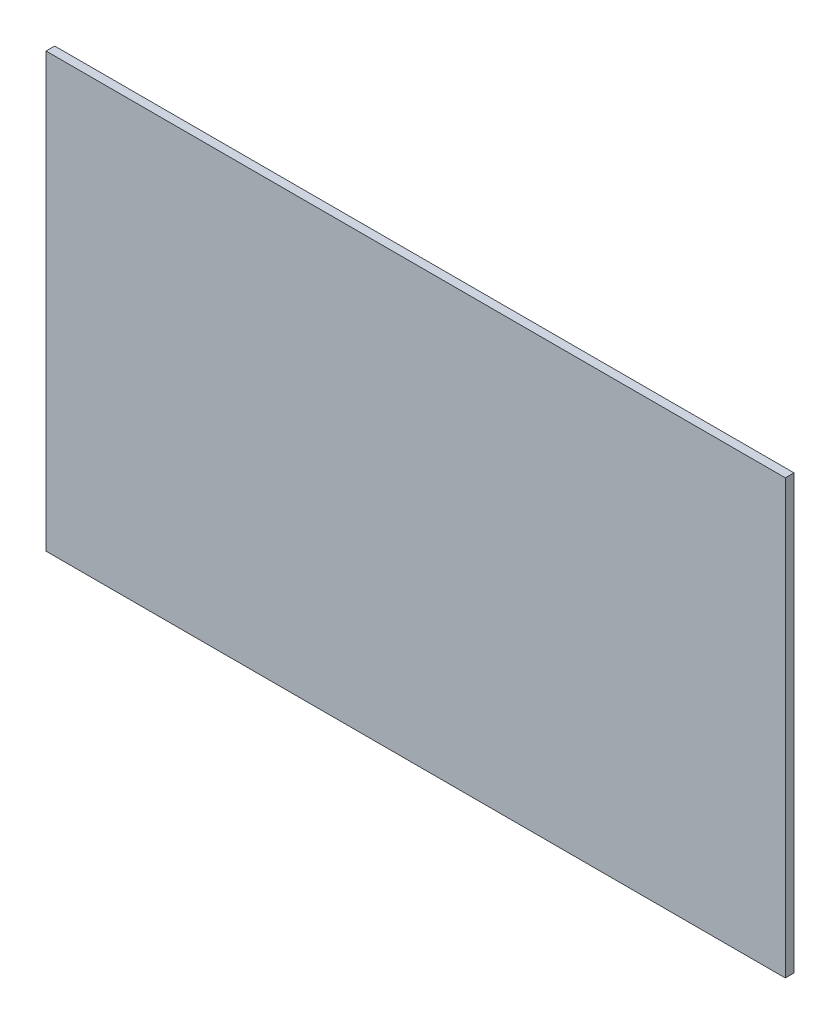
SolidWorks part; units mm, degrees
ref_plane "Front Plane" through (0, 0, 0) normal (0, 0, 1) x (1, 0, 0)
ref_plane "Top Plane" through (0, 0, 0) normal (0, 1, 0) x (1, 0, 0)
ref_plane "Right Plane" through (0, 0, 0) normal (1, 0, 0) x (0, 0, -1)
sketch "Sketch1" plane through (0, 0, 0) normal (0, 0, 1) x (1, 0, 0)
  line L1 (-128, -75) -> (128, -75)
  line L2 (-128, -75) -> (-128, 75)
  line L3 (-128, 75) -> (128, 75)
  line L4 (128, -75) -> (128, 75)
  line L5 (-128, -75) -> (128, 75) construction
  line L6 (-128, 75) -> (128, -75) construction
  point P0 (0, 0)
  dimension "D1" = 256
  dimension "D2" = 150
extrude "Boss-Extrude1" add sketch "Sketch1" along normal blind 3
